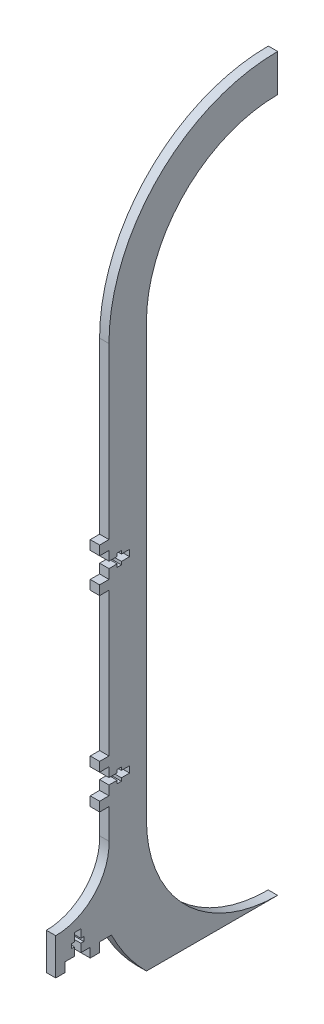
SolidWorks part; units mm, degrees
ref_plane "Front Plane" through (0, 0, 0) normal (0, 0, 1) x (1, 0, 0)
ref_plane "Top Plane" through (0, 0, 0) normal (0, 1, 0) x (1, 0, 0)
ref_plane "Right Plane" through (0, 0, 0) normal (1, 0, 0) x (0, 0, -1)
sketch "Elevator Ball Support Rail" plane through (0, 0, 0) normal (1, 0, 0) x (0, 0, -1)
  line L0 (88.9, 234.95) -> (88.9, 260.35)
  line L1 (-31.75, -125.73) -> (-25.4, -125.73)
  line L2 (88.9, -234.95) -> (0, -234.95)
  line L3 (-31.75, -201.93) -> (-23.7226, -201.93)
  line L6 (0, 146.05) -> (0, -146.05)
  line L7 (-25.4, -146.05) -> (-25.4, -201.93) construction
  line L8 (0, -146.05) -> (0, -234.95) construction
  line L12 (-61.468, -183.4476) -> (-61.468, -201.93)
  line L42 (0, 0) -> (-25.4, 0) construction
  line L46 (-25.4, 1.27) -> (-25.4, -96.012)
  line L47 (-25.4, -96.012) -> (-31.75, -96.012)
  line L48 (-25.4, -102.362) -> (-25.4, -108.712)
  line L49 (-31.75, -96.012) -> (-31.75, -102.362)
  line L50 (-31.75, -102.362) -> (-25.4, -102.362)
  line L51 (-25.4, -108.712) -> (-19.865, -108.712)
  line L52 (-19.865, -108.712) -> (-19.865, -106.671)
  line L53 (-19.865, -106.671) -> (-16.965, -106.671)
  line L54 (-16.965, -106.671) -> (-16.965, -108.712)
  line L55 (-16.965, -108.712) -> (-11.43, -108.712)
  line L56 (-11.43, -108.712) -> (-11.43, -113.03)
  line L57 (-11.43, -113.03) -> (-16.965, -113.03)
  line L58 (-16.965, -113.03) -> (-16.965, -115.071)
  line L59 (-16.965, -115.071) -> (-19.865, -115.071)
  line L60 (-19.865, -115.071) -> (-19.865, -113.03)
  line L61 (-19.865, -113.03) -> (-25.4, -113.03)
  line L62 (-25.4, -113.03) -> (-25.4, -119.38)
  line L63 (-25.4, -119.38) -> (-31.75, -119.38)
  line L64 (-31.75, -119.38) -> (-31.75, -125.73)
  line L66 (-25.4, -125.73) -> (-25.4, -146.05)
  line L68 (-25.4, 30.988) -> (-25.4, 146.05)
  arc A0 (0, 146.05) -> (88.9, 234.95) centre (88.9, 146.05) cw
  arc A1 (88.9, 260.35) -> (-25.4, 146.05) centre (88.9, 146.05) ccw
  arc A2 (0, -146.05) -> (88.9, -234.95) centre (88.9, -146.05) ccw
  arc A3 (-23.7226, -201.93) -> (0, -234.95) centre (88.9, -146.05) ccw
  arc A4 (-61.468, -183.4476) -> (-25.4, -146.05) centre (-61.468, -147.356) ccw
  point P4 (0, 0)
  line B0 (-55.118, -201.93) -> (-55.118, -208.28)
  line B1 (-55.118, -208.28) -> (-61.468, -208.28)
  line B2 (-61.468, -208.28) -> (-61.468, -201.93)
  line B3 (-48.768, -201.93) -> (-48.768, -196.395)
  line B4 (-48.768, -196.395) -> (-50.809, -196.395)
  line B5 (-50.809, -196.395) -> (-50.809, -193.495)
  line B6 (-50.809, -193.495) -> (-48.768, -193.495)
  line B7 (-48.768, -193.495) -> (-48.768, -187.96)
  line B8 (-48.768, -187.96) -> (-44.45, -187.96)
  line B9 (-44.45, -187.96) -> (-44.45, -193.495)
  line B10 (-44.45, -193.495) -> (-42.409, -193.495)
  line B11 (-42.409, -193.495) -> (-42.409, -196.395)
  line B12 (-42.409, -196.395) -> (-44.45, -196.395)
  line B13 (-44.45, -196.395) -> (-44.45, -201.93)
  line B14 (-46.609, -187.96) -> (-46.609, -201.93) construction
  line B15 (-38.1, -201.93) -> (-44.45, -201.93)
  line B16 (-31.75, -208.28) -> (-31.75, -201.93)
  line B17 (-55.118, -201.93) -> (-48.768, -201.93)
  line B18 (-38.1, -208.28) -> (-31.75, -208.28)
  line B19 (-38.1, -201.93) -> (-38.1, -208.28)
  line B20 (-25.4, 24.638) -> (-31.75, 24.638)
  line B21 (-31.75, 24.638) -> (-31.75, 30.988)
  line B22 (-31.75, 30.988) -> (-25.4, 30.988)
  line B23 (-25.4, 18.288) -> (-19.865, 18.288)
  line B24 (-19.865, 18.288) -> (-19.865, 20.329)
  line B25 (-19.865, 20.329) -> (-16.965, 20.329)
  line B26 (-16.965, 20.329) -> (-16.965, 18.288)
  line B27 (-16.965, 18.288) -> (-11.43, 18.288)
  line B28 (-11.43, 18.288) -> (-11.43, 13.97)
  line B29 (-11.43, 13.97) -> (-16.965, 13.97)
  line B30 (-16.965, 13.97) -> (-16.965, 11.929)
  line B31 (-16.965, 11.929) -> (-19.865, 11.929)
  line B32 (-19.865, 11.929) -> (-19.865, 13.97)
  line B33 (-19.865, 13.97) -> (-25.4, 13.97)
  line B34 (-11.43, 16.129) -> (-25.4, 16.129) construction
  line B35 (-25.4, 7.62) -> (-25.4, 13.97)
  line B36 (-31.75, 1.27) -> (-25.4, 1.27)
  line B37 (-25.4, 24.638) -> (-25.4, 18.288)
  line B38 (-31.75, 7.62) -> (-31.75, 1.27)
  line B39 (-25.4, 7.62) -> (-31.75, 7.62)
  dimension "D5" = 25.4
  dimension "D4" = 88.9
  dimension "D7" = 88.9
  dimension "D8" = 26.67
  dimension "D6" = 203.2
  dimension "D1" = 6.35
  dimension "D3" = 292.1
  dimension "D9" = 40.604
  dimension "D20" = 55.88
  dimension "D28" = 6.35
  dimension "D29" = 4.318
  dimension "D30" = 2.9
  dimension "D31" = 13.97
  dimension "D32" = 6.35
  dimension "D33" = 8.4
  dimension "D34" = 6.35
  dimension "D36" = 25.4
  dimension "D37" = 76.2
sketch_block_instance "Male T-slot assembly-1"
sketch_block "Male T-slot assembly" parameters "D1"=6.35, "D2"=6.35, "D3"=4.318, "D4"=2.9, "D5"=8.4, "D6"=13.97, "D7"=6.35
sketch_block_instance "Male T-slot assembly-5"
extrude "Boss-Extrude2" add sketch "Elevator Ball Support Rail" along normal blind 6.35 contours A4 L12 L3 A3 L2 A2 L6 A0 L0 A1 L46 L47 L49 L50 region at (0, -1.8755, 1.628)
equation "\"Ball Diameter\"= 1.75in"
equation "\"Pulley Diameter\" = 1in"
equation "\"Reactor Height\" = 14in"
equation "\"Sheet Thickness\"= 0.25in"
equation "\"Screw Diameter\"= .17in"
equation "\"Robot Diameter\"= 14in"
equation "\"Castor Screw Diameter\"= 0.22in"
equation "\"Wheel Diameter\" = 4in"
equation "\"Nut Diameter\" = 8.4mm"
equation "\"Nut Height\" = 2.9mm"
equation "\"Screw Height\" = 0.55in"
equation "\"D11@Elevator Ball Support Rail\"=\"Sheet Thickness\""
equation "\"Elevator Height\" = 11.5in"
equation "\"D7@Elevator Ball Support Rail\" = \"Elevator Clearance from Axis\""
equation "\"D13@Elevator Ball Support Rail\"=\"Sheet Thickness\""
equation "\"D1@T-Slot\" = \"Screw Diameter\""
equation "\"D16@Elevator Ball Support Rail\"=\"Nut Diameter\""
equation "\"D15@Elevator Ball Support Rail\"=\"Nut Height\""
equation "\"D1@Boss-Extrude2\"=\"Sheet Thickness\""
equation "\"D3@Elevator Ball Support Rail\"=\"Elevator Height\""
equation "\"Elevator Width\" = \"Ball Diameter\" + 0.25in"
equation "\"Elevator Bearing Diameter\" = sqr(2*(\"Sheet Thickness\"^2)) + 0.2in"
equation "\"Elevator Axle Endcap Diameter\" = \"Pulley Diameter\" + 0.25in"
equation "\"Elevator Axle Length\" = \"Elevator Width\" + 8*\"Sheet Thickness\""
equation "\"Elevator Clearance from Axis\" = 3.5in"
equation "\"D4@Elevator Ball Support Rail\"=\"Elevator Clearance from Axis\""
equation "\"D32@Elevator Ball Support Rail\"=\"Sheet Thickness\""
equation "\"D33@Elevator Ball Support Rail\"=\"Nut Diameter\""
equation "\"D34@Elevator Ball Support Rail\"=\"Sheet Thickness\""
equation "\"D30@Elevator Ball Support Rail\"=\"Nut Height\""
equation "\"D28@Elevator Ball Support Rail\"=\"Sheet Thickness\""
equation "\"D29@Elevator Ball Support Rail\"=\"Screw Diameter\""
equation "\"D31@Elevator Ball Support Rail\" = \"Screw Height\""
equation "\"D1@Elevator Ball Support Rail\"=\"Sheet Thickness\""
equation "\"Ball Radius\" = \"Ball Diameter\"/2"
equation "\"Elevator Horizontal Clearance\" = \"Elevator Width\" + 0.5in"
equation "\"Claw Horizontal Seperation\" = (\"Elevator Width\"/2) - (1.5 * \"Sheet Thickness\") - 0.15in"
equation "\"Claw Radius\" = \"Ball Radius\" + 0.1in"
equation "\"Castor Wheel Height\" = 1.25in"
equation "\"D8@Elevator Ball Support Rail\"=\"Castor Wheel Height\"-0.2in"
